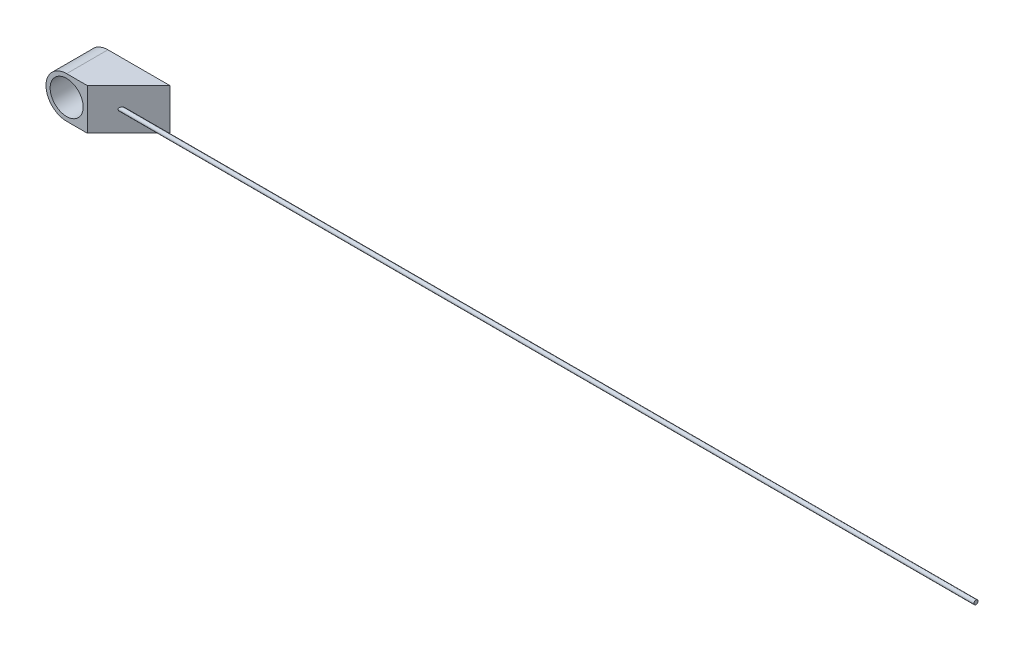
SolidWorks part; units mm, degrees
ref_plane "Płaszczyzna przednia" through (0, 0, 0) normal (0, 0, 1) x (1, 0, 0)
ref_plane "Płaszczyzna górna" through (0, 0, 0) normal (0, 1, 0) x (1, 0, 0)
ref_plane "Płaszczyzna prawa" through (0, 0, 0) normal (1, 0, 0) x (0, 0, -1)
sketch "Szkic1" plane through (0, 0, 0) normal (0, 0, 1) x (1, 0, 0)
  circle A0 centre (0, 0) radius 4
  circle A1 centre (0, 0) radius 5
extrude "Dodanie-wyciągnięcie1" add sketch "Szkic1" along normal blind 10
sketch "Szkic2" plane through (0, 0, 10) normal (0, 0, 1) x (1, 0, 0)
  line L1 (5, 5) -> (15, 5)
  line L2 (5, 5) -> (5, -5)
  line L3 (5, -5) -> (15, -5)
  line L4 (15, 5) -> (15, -5)
  point P4 (0, 0)
extrude "Dodanie-wyciągnięcie2" add sketch "Szkic2" against normal blind 10 separate body
sketch "Szkic3" plane through (0, 0, 0) normal (0, 0, 1) x (1, 0, 0)
  line L0 (0, 5) -> (5, 5)
  line L1 (5, 5) -> (5, 0)
  line L2 (5, 5) -> (5, -5) construction
  line L3 (5, 0) -> (3.3573, 3.7052)
  line L4 (3.3573, 3.7052) -> (0, 5)
  circle A0 centre (0, 0) radius 5 construction
  point P5 (0, 0)
extrude "Dodanie-wyciągnięcie3" add sketch "Szkic3" along normal blind 10
sketch "Szkic5" plane through (0, 0, 0) normal (0, 0, -1) x (-1, 0, 0)
  line L0 (-5, -5) -> (-5, 0)
  line L1 (-5, 0) -> (-5, -5) construction
  line L2 (-5, 0) -> (-3.1052, -3.9189)
  line L3 (-3.1052, -3.9189) -> (0, -5)
  line L4 (0, -5) -> (-5, -5)
  arc A0 (-5, 0) -> (0, 5) centre (0, 0) ccw construction
extrude "Dodanie-wyciągnięcie4" add sketch "Szkic5" against normal blind 10
chamfer "Sfazowanie1" distance 10 angle 45 1 edges at (15, 0, 10)
sketch "Szkic6" plane through (0, 0, 0) normal (1, 0, 0) x (0, 0, -1)
  circle A0 centre (-5.7854, 0) radius 0.5
extrude "Dodanie-wyciągnięcie6" add sketch "Szkic6" along normal blind 210 from offset 6
